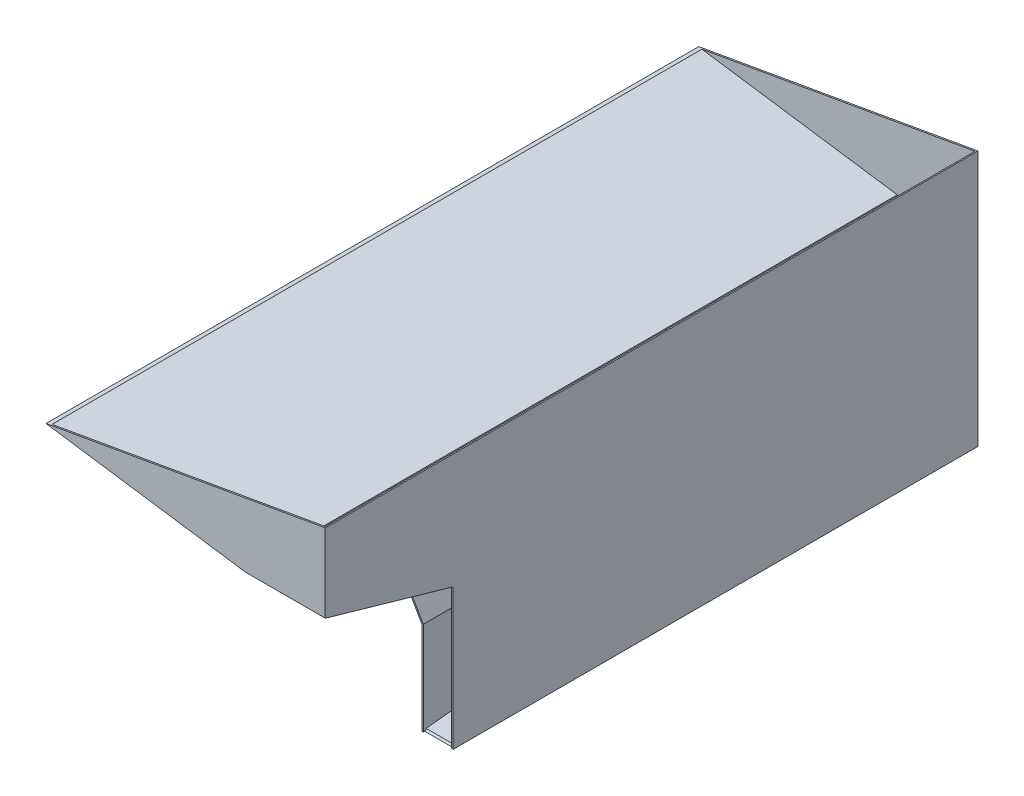
SolidWorks part; units mm, degrees
ref_plane "Front Plane" through (0, 0, 0) normal (0, 0, 1) x (1, 0, 0)
ref_plane "Top Plane" through (0, 0, 0) normal (0, 1, 0) x (1, 0, 0)
ref_plane "Right Plane" through (0, 0, 0) normal (1, 0, 0) x (0, 0, -1)
other "Center of Mass"
sketch "Sketch2" plane through (0, 0, 0) normal (0, 0, 1) x (1, 0, 0)
  line L0 (0, 0) -> (-105, 181.8653)
  line L1 (-105, 181.8653) -> (-532.9388, 244.1441)
  line L2 (-532.9388, 244.1441) -> (67.4, 350)
  line L3 (67.4, 350) -> (67.4, -200)
  line L4 (67.4, -200) -> (0, -200)
  line L5 (0, -200) -> (0, 0)
  dimension "D1" = 150
  dimension "D2" = 609.6
  dimension "D3" = 550
  dimension "D4" = 200
  dimension "D5" = 67.4
  dimension "D6" = 210
  dimension "D7" = 280
extrude "Boss-Extrude1" add sketch "Sketch2" along normal mid plane 1403.35
shell "Shell1" thickness 3.175 removed face at (-232.7694, 297.072, 0)
sketch "Sketch3" plane through (0, 0, 701.675) normal (0, 0, 1) x (1, 0, 0)
  line L1 (12.7, -187.3) -> (54.7, -187.3)
  line L2 (12.7, -187.3) -> (12.7, 102.7)
  line L3 (12.7, 102.7) -> (54.7, 102.7)
  line L4 (54.7, -187.3) -> (54.7, 102.7)
  line L6 (0, -200) -> (67.4, -200) construction
  point P6 (33.7, -200)
  point P7 (33.7, -187.3)
  dimension "D1" = 42
  dimension "D2" = 12.7
  dimension "D3" = 290
extrude "Cut-Extrude1" cut sketch "Sketch3" against normal blind 20
scale "Scale1" [suppressed]
sketch "Sketch6" plane through (0, 0, 701.675) normal (0, 0, 1) x (1, 0, 0)
  line L1 (-167.2364, 157.2102) -> (-3.283, 157.2102)
  line L2 (-167.2364, 157.2102) -> (-167.2364, -5.4179)
  line L3 (-167.2364, -5.4179) -> (-3.283, -5.4179)
  line L4 (-3.283, 157.2102) -> (-3.283, -5.4179)
extrude "Cut-Extrude3" [suppressed] cut sketch "Sketch6" against normal blind 200
sketch "Sketch7" plane through (0, 0, 0) normal (-1, 0, 0) x (0, 0, 1)
  line L1 (701.675, -200) -> (426.675, -200)
  line L2 (701.675, -200) -> (701.675, 102.7)
  line L3 (701.675, 102.7) -> (426.675, 102.7)
  line L4 (426.675, -200) -> (426.675, 102.7)
  dimension "D1" = 275
  dimension "D2" = 302.7
extrude "Cut-Extrude5" cut sketch "Sketch7" against normal mid plane 200
sketch "Sketch9" plane through (67.4, 0, 0) normal (1, 0, 0) x (0, 0, -1)
  line L0 (-701.675, 102.7) -> (-701.675, 350) construction
  line L1 (-426.675, 102.7) -> (-701.675, 102.7)
  line L2 (-426.675, 102.7) -> (-426.675, 181.7)
  line L3 (-426.675, 181.7) -> (-701.675, 181.7)
  line L4 (-701.675, 102.7) -> (-701.675, 181.7)
  line L5 (-701.675, 181.7) -> (-426.675, 102.7)
  line M2 (-701.675, 102.7) -> (-426.675, 102.7)
  line M7 (-701.675, 350) -> (-701.675, 102.7)
  dimension "D1" = 79
extrude "Cut-Extrude7" cut sketch "Sketch9" against normal through all contours L5 M7 M2 region at (67.4, 129.0333, 610.0083)
sketch "Sketch11" plane through (0, -18.3572, 5.2735) normal (0, -0.9611, 0.2761) x (1, 0, 0)
  line L0 (67.4, 724.5674) -> (67.4, 438.445)
  line L1 (67.4, 438.445) -> (-59.2939, 438.445)
  line L2 (-59.2939, 438.445) -> (-104.9045, 724.5674)
  line L3 (-104.9045, 724.5674) -> (67.4, 724.5674)
extrude "Boss-Extrude3" add sketch "Sketch11" against normal blind 6.35
sketch "Sketch12" plane through (3.175, 0, 0) normal (1, 0, 0) x (0, 0, -1)
  line L0 (-426.675, -196.825) -> (688.975, -79.5655)
  line L1 (688.975, -79.5655) -> (688.975, -196.825)
  line L2 (688.975, -196.825) -> (-426.675, -196.825)
  line L3 (701.675, -200) -> (701.675, 350) construction
  dimension "D1" = 3.175
  dimension "D2" = 12.7
  dimension "D3" = 6
extrude "Boss-Extrude4" add sketch "Sketch12" along normal up to surface (61.05 mm away) up to face at (64.225, 100.5897, 182.6102)
chamfer "Chamfer1" distance 6.35 angle 45 1 edges at (33.7, -196.825, 426.675) first distance on face at (33.7, -138.1952, -131.15)
